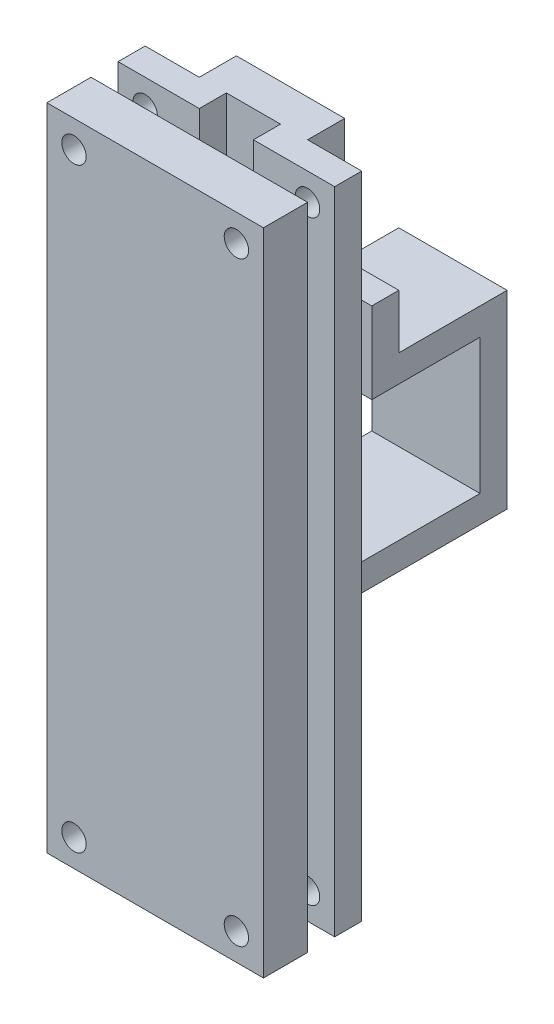
SolidWorks part; units mm, degrees
ref_plane "Front Plane" through (0, 0, 0) normal (0, 0, 1) x (1, 0, 0)
ref_plane "Top Plane" through (0, 0, 0) normal (0, 1, 0) x (1, 0, 0)
ref_plane "Right Plane" through (0, 0, 0) normal (1, 0, 0) x (0, 0, -1)
sketch "Sketch1" plane through (0, 0, 0) normal (0, 1, 0) x (1, 0, 0)
  line L0 (10, 25) -> (30, 25) construction
  line L9 (0, 0) -> (40, 0)
  line L10 (0, 0) -> (0, 8.15)
  line L11 (10, 55) -> (30, 55)
  line L12 (40, 0) -> (40, 8.15)
  line L14 (10, 55) -> (10, 18.15)
  line L18 (30, 55) -> (30, 18.15)
  line L22 (15, 13.15) -> (15, 18.15)
  line L23 (15, 18.15) -> (25, 18.15)
  line L24 (25, 13.15) -> (25, 18.15)
  line L25 (10, 50) -> (30, 50) construction
  line L26 (0, 8.15) -> (40, 8.15)
  line L27 (10, 18.15) -> (0, 18.15)
  line L30 (0, 18.15) -> (0, 13.15)
  line L32 (30, 18.15) -> (40, 18.15)
  line L33 (40, 18.15) -> (40, 13.15)
  line L40 (40, 13.15) -> (25, 13.15)
  line L41 (15, 13.15) -> (0, 13.15)
  dimension "D2" = 25
  dimension "D3" = 5
  dimension "D4" = 5
  dimension "D5" = 10
  dimension "D6" = 20
  dimension "D7" = 10
  dimension "D8" = 5
  dimension "D9" = 6.85
  dimension "D10" = 5
  dimension "D11" = 5
  dimension "D12" = 8.15
  dimension "D13" = 10
  dimension "D14" = 5
extrude "Boss-Extrude1" add sketch "Sketch1" along normal blind 120
sketch "Sketch3" plane through (30, 0, 0) normal (1, 0, 0) x (0, 0, -1)
  line L0 (18.15, 120) -> (55, 120) construction
  line L1 (25, 120) -> (55, 120)
  line L2 (25, 120) -> (25, 77.5)
  line L3 (35, 77.5) -> (55, 77.5)
  line L4 (55, 120) -> (55, 77.5)
  line L5 (55, 120) -> (55, 0) construction
  line L6 (55, 0) -> (18.15, 0) construction
  line L7 (55, 42.5) -> (25, 42.5)
  line L8 (55, 42.5) -> (55, 0)
  line L9 (55, 0) -> (25, 0)
  line L10 (25, 42.5) -> (25, 0)
  line L12 (30, 72.5) -> (50, 72.5)
  line L13 (25, 72.5) -> (25, 47.5)
  line L14 (25, 47.5) -> (50, 47.5)
  line L15 (50, 72.5) -> (50, 47.5)
  line L16 (30, 87.5) -> (35, 87.5)
  line L17 (35, 87.5) -> (35, 77.5)
  line L19 (25, 77.5) -> (25, 72.5)
  line L20 (30, 87.5) -> (30, 72.5)
  point P18 (50, 60)
  dimension "D1" = 25
  dimension "D2" = 25
  dimension "D3" = 5
  dimension "D4" = 5
  dimension "D5" = 5
  dimension "D6" = 60
  dimension "D7" = 15
  dimension "D8" = 5
  dimension "D9" = 5
extrude "Cut-Extrude2" cut sketch "Sketch3" against normal blind 120
hole_wizard "Ø4.5 (4.5) Diameter Hole1" positions "Sketch4" profile "Sketch5" hole size "Ø4.5" standard "ANSI Metric" end condition through all
sketch "Sketch4" plane through (0, 0, -18.15) normal (0, 0, -1) x (-1, 0, 0)
  line L0 (-40, 120) -> (-30, 120) construction
  line L1 (-40, 120) -> (-40, 0) construction
  line L2 (0, 120) -> (0, 0) construction
  line L3 (-10, 120) -> (0, 120) construction
  line L4 (-15, 0) -> (0, 0) construction
  line L5 (-40, 0) -> (-25, 0) construction
  point P0 (-35, 5)
  point P2 (-5, 5)
  point P4 (-5, 115)
  point P6 (-35, 115)
  dimension "D1" = 5
  dimension "D2" = 5
  dimension "D3" = 5
  dimension "D4" = 5
  dimension "D5" = 5
  dimension "D6" = 5
  dimension "D7" = 5
  dimension "D8" = 5
sketch "Sketch5" plane through (35, 5, -18.15) normal (1, 0, 0) x (0, 1, 0)
  line L0 (0, 0) -> (0, 18.15)
  line L1 (0, 18.15) -> (2.25, 18.15)
  line L2 (2.25, 18.15) -> (2.25, 0.025)
  line L3 (2.25, 0.025) -> (2.275, 0)
  line L5 (2.275, 0) -> (0, 0)
  line L6 (-2.25, 0.025) -> (-2.275, 0) construction
  line L11 (0, -6.35) -> (0, 107.95) construction
  dimension "Thru Hole Dia." = 4.5
  dimension "Thru Hole Depth" = 18.15
  dimension "Near C'Sink Dia." = 4.55
  dimension "Near C'Sink Angle" = 90
